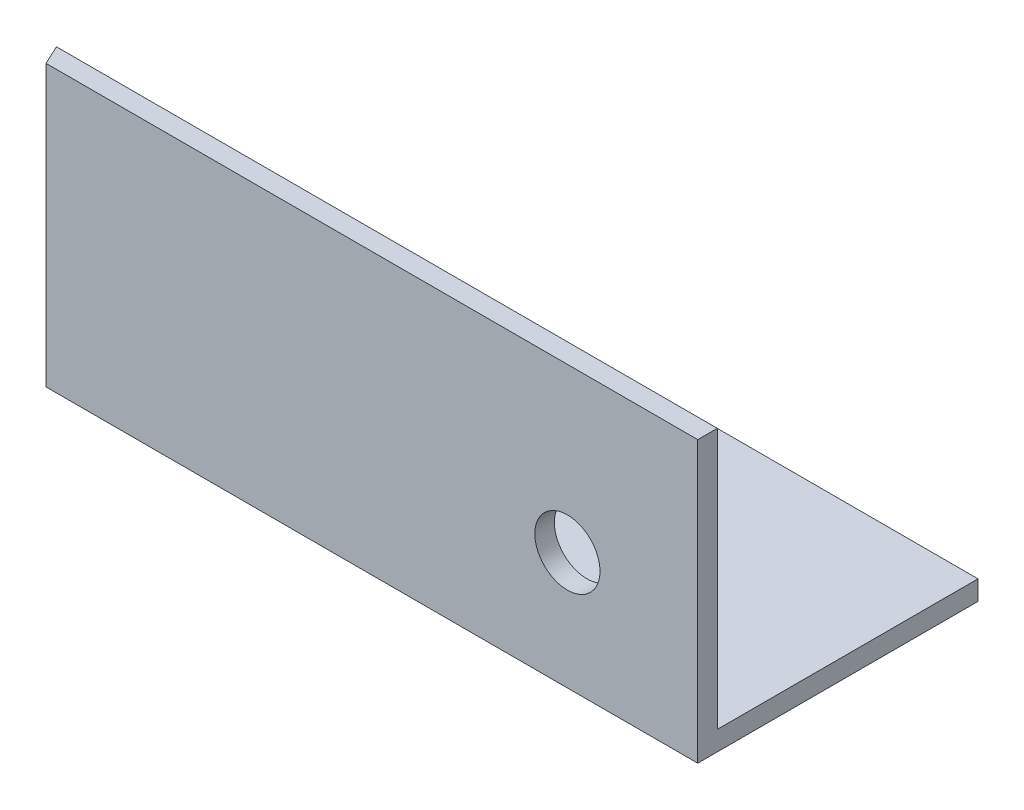
SolidWorks part; units mm, degrees
ref_plane "Спереди" through (0, 0, 0) normal (0, 0, 1) x (1, 0, 0)
ref_plane "Сверху" through (0, 0, 0) normal (0, 1, 0) x (1, 0, 0)
ref_plane "Справа" through (0, 0, 0) normal (1, 0, 0) x (0, 0, -1)
sketch "Эскиз1" plane through (0, 0, 0) normal (1, 0, 0) x (0, 0, -1)
  line L0 (0, 40) -> (0, 0)
  line L1 (0, 0) -> (40, 0)
extrude "Вытянуть-Тонкостенный1" add sketch "Эскиз1" along normal blind 120 thin thin type one direction wall 3
sketch "Эскиз2" plane through (0, -3, 0) normal (0, 1, 0) x (1, 0, 0)
  line L0 (0, 40) -> (20, -3)
  line L2 (20, -3) -> (0, -3)
  line L3 (0, -3) -> (0, 40)
  line L4 (120, 40) -> (0, 40) construction
  line L5 (120, -3) -> (0, -3) construction
extrude "Вырез-Вытянуть1" cut sketch "Эскиз2" along normal blind 50
sketch "Эскиз3" plane through (0, 0, 3) normal (0, 0, 1) x (1, 0, 0)
  circle A0 centre (100, 15) radius 5
extrude "Вырез-Вытянуть2" cut sketch "Эскиз3" against normal blind 10
